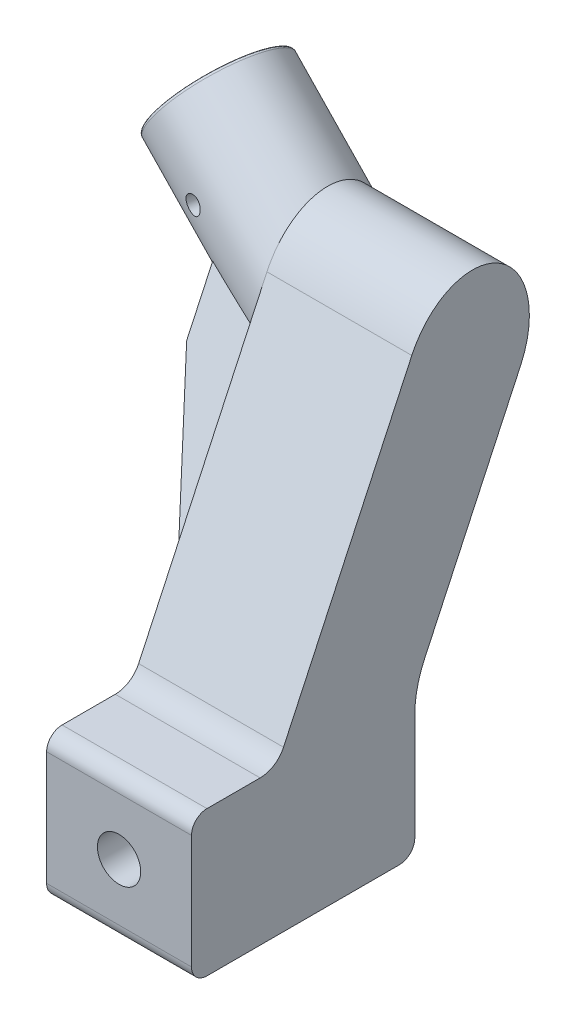
SolidWorks part; units mm, degrees
ref_plane "Front Plane" through (0, 0, 0) normal (0, 0, 1) x (1, 0, 0)
ref_plane "Top Plane" through (0, 0, 0) normal (0, 1, 0) x (1, 0, 0)
ref_plane "Right Plane" through (0, 0, 0) normal (1, 0, 0) x (0, 0, -1)
sketch "Sketch14" plane through (0, 0, 0) normal (0, 0, 1) x (1, 0, 0)
  line L0 (0, 0) -> (0, -50000) construction
ref_plane "Plane4" through (0, 0, 0) normal (0.1736, 0, -0.9848) x (0, -1, 0)
sketch "Sketch1" plane through (0, 0, 0) normal (0.1736, 0, -0.9848) x (-0.9848, 0, -0.1736)
  line L4 (0, 0) -> (24.9266, 16.6932)
  dimension "D1" = 33.81
  dimension "D2" = 30
ref_plane "Plane1" through (-24.5479, 16.6932, -4.3285) normal (-0.8183, 0.5564, -0.1443) x (-0.1196, -0.4103, -0.9041)
sketch "Sketch2" plane through (-24.5479, 16.6932, -4.3285) normal (-0.8183, 0.5564, -0.1443) x (-0.1196, -0.4103, -0.9041)
  circle A0 centre (0, 0) radius 10.05
  circle A1 centre (0, 0) radius 12.05
  dimension "D1" = 20.1
  dimension "D2" = 2
extrude "Boss-Extrude1" add sketch "Sketch2" against normal up to surface (36.9065 mm away) up to plane "Right Plane"
sketch "Sketch6" plane through (0, 0, 0) normal (0, 0, 1) x (1, 0, 0)
  line L0 (-31.3239, 6.7289) -> (-17.7719, 26.6576) construction
  line L1 (0, 14.5722) -> (-17.7719, 26.6576) construction
  line L2 (-31.3239, 6.7289) -> (0, -14.5722) construction
  line L3 (-24.5479, 16.6932) -> (-24.5479, -64.2099) construction
  dimension "D1" = 80.9031
sketch "Sketch15" plane through (0, 0, 0) normal (0.1736, 0, -0.9848) x (0, -1, 0)
  line L0 (0, 0) -> (-16.6932, 24.9266) construction
  line L1 (-6.681, 31.6317) -> (-26.7054, 18.2215) construction
  line L2 (-16.6932, 24.9266) -> (-1.4229, 2.1247) construction
  circle A1 centre (-9.0581, 13.5257) radius 1.7
  ellipse E0 centre (0, 0) end of major axis (-14.5722, 0.2119) minor radius 2.1144 construction
  dimension "D1" = 3.4
extrude "Cut-Extrude4" cut sketch "Sketch15" against normal through all both and the other way through all
sketch "Sketch4" plane through (0, 0, 0) normal (1, 0, 0) x (0, 0, -1)
  line L23 (-36.7934, -50.1599) -> (-53.2934, -50.1599)
  line L28 (-10.5643, 6.0887) -> (-36.7934, -50.1599)
  line L29 (-53.2934, -50.1599) -> (-53.2934, -78.2599)
  line L30 (-36.7934, -50.1599) -> (-9.9865, -50.1599) construction
  line L31 (-9.9865, -50.1599) -> (10.5643, -6.0887)
  line L32 (-53.2934, -78.2599) -> (-36.7934, -78.2599)
  line L34 (-36.7934, -50.1599) -> (-9.9865, -50.1599) construction
  line L35 (-36.7934, -50.1599) -> (-36.7934, -78.2599) construction
  line L36 (-36.7934, -78.2599) -> (-9.9865, -78.2599)
  line L37 (-9.9865, -50.1599) -> (-9.9865, -78.2599)
  line L38 (-36.7934, -50.1599) -> (-9.9865, -78.2599) construction
  line L39 (-36.7934, -78.2599) -> (-9.9865, -50.1599) construction
  ellipse E0 centre (0, 0) end of major axis (3.6962, 14.2549) minor radius 12.05 construction
  ellipse E1 centre (0, 0) end of major axis (3.6962, 14.2549) minor radius 12.05 (10.5643, -6.0887) -> (-10.5643, 6.0887) ccw
  point P16 (-23.39, -64.2099)
  ellipse M1 centre (0, 0) end of major axis (3.6962, 14.2549) minor radius 12.05
  ellipse M2 centre (0, 0) end of major axis (3.0827, 11.8889) minor radius 10.05
  dimension "D1" = 25
  dimension "D2" = 14.05
  dimension "D3" = 28.1
  dimension "D4" = 16.5
extrude "Boss-Extrude2" add sketch "Sketch4" along normal blind 28.098 contours M1 M2 | M2 | M1 | M1 | M2 region at (0, -48.2431, 23.7209) region at (0, 12.4356, 4.636) region at (0, 0, 0)
sketch "Sketch10" plane through (0, 0, 9.9865) normal (0, 0, -1) x (-1, 0, 0)
  line L1 (-28.098, -78.2599) -> (0, -78.2599) construction
  line L6 (0, -78.2599) -> (0, -50.1599)
  line L7 (0, -50.1599) -> (-28.098, -50.1599)
  line L12 (-28.098, -50.1599) -> (-28.098, -78.2599)
  line L13 (-28.098, -78.2599) -> (0, -78.2599)
  line L14 (0, -78.2599) -> (0, -50.1599) construction
  line L15 (0, -50.1599) -> (-28.098, -50.1599) construction
  line L16 (-28.098, -50.1599) -> (-28.098, -78.2599) construction
  line L17 (-28.098, -78.2599) -> (0, -78.2599) construction
  circle A0 centre (-14.049, -64.2099) radius 11.074
  point P16 (-14.049, -78.2599)
  dimension "D2" = 22.148
  dimension "D3" = 0
  dimension "D1" = 14.05
extrude "Cut-Extrude2" cut sketch "Sketch10" against normal blind 7.874 and the other way through all
sketch "Sketch11" plane through (0, 0, 17.8605) normal (0, 0, -1) x (-1, 0, 0)
  circle A0 centre (-14.049, -64.2099) radius 4.2
  circle A1 centre (-14.049, -64.2099) radius 11.074
  circle A2 centre (-14.049, -64.2099) radius 11.074 construction
  dimension "D2" = 8.4
  dimension "D1" = 0
extrude "Cut-Extrude3" cut sketch "Sketch11" against normal through all both and the other way through all
ref_plane "Plane3" through (0, 0, 0) normal (0, -0.4226, -0.9063) x (1, 0, 0)
sketch "Sketch12" plane through (0, 0, 0) normal (0, -0.4226, -0.9063) x (1, 0, 0)
  line L0 (0, 49.6808) -> (0, 1.0535) construction
  line L2 (0, 47.0416) -> (0, 14.6458)
  line L4 (-11.7911, 14.6458) -> (0, 47.0416)
  line L5 (-11.7911, 14.6458) -> (0, 14.6458)
  dimension "D1" = 11.08
  dimension "D2" = 20
fillet "Fillet8" radius 20 1 edges at (14.049, -50.1599, 9.9865)
fillet "Fillet9" radius 3 3 edges at (14.049, -78.2599, 9.9865) (14.049, -50.1599, 53.2934) (14.049, -78.2599, 53.2934)
fillet "Fillet10" radius 0.5 2 edges at (-31.3239, 6.7289, -4.3285) (-30.1993, 8.3827, -4.3285)
fillet "Fillet11" radius 5 1 edges at (14.049, -50.1599, 36.7934)
extrude "Boss-Extrude6" add sketch "Sketch12" along normal mid plane 18
sketch "Sketch13" plane through (0, -13.2736, 6.1896) normal (0, 0.9063, -0.4226) x (1, 0, 0)
  line L5 (-11.7911, -9) -> (0, -9)
  line L6 (0, -9) -> (0, 0.8738)
  line L7 (0, 0.8738) -> (0, 9)
  line L8 (0, 9) -> (-11.7911, 9)
  line L9 (-11.7911, 9) -> (-11.7911, -9)
  line L10 (-11.7911, -9) -> (0, -9)
  line L11 (0, -9) -> (0, 0.8738)
  line L12 (0, 0.8738) -> (0, 9)
  line L13 (0, 9) -> (-11.7911, 9)
  line L14 (-11.7911, 9) -> (-11.7911, -9)
  dimension "D1" = 0
extrude "Boss-Extrude7" add sketch "Sketch13" along normal up to surface (4.0541 mm away) up to face at (-30.9148, 6.4507, -4.2563)
ref_plane "Plane2" [suppressed] through (0, 0, 15) normal (0, 0, 1) x (1, 0, 0)
mirror "Mirror1" [suppressed] about plane through (0, 0, 15) normal (0, 0, 1) of bodies 107
delete or keep bodies "Body-Delete/Keep 1" [suppressed] type delete bodies bodies 107
